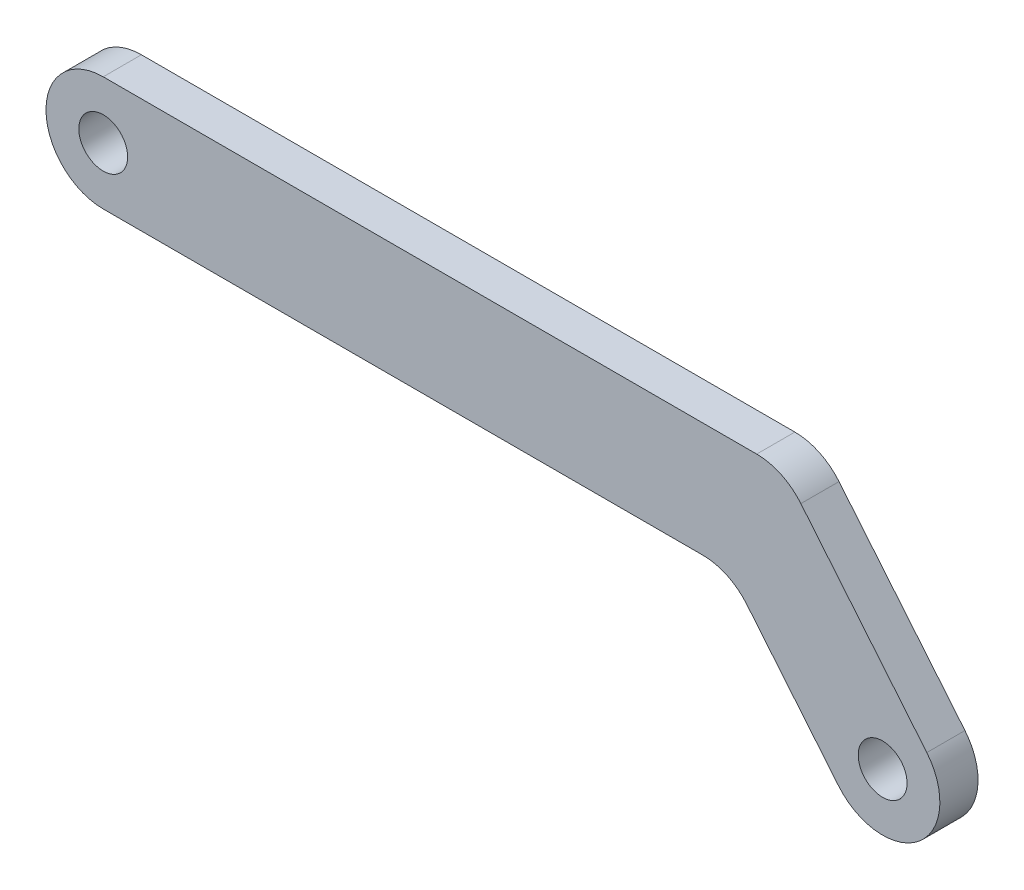
SolidWorks part; units mm, degrees
ref_plane "Front Plane" through (0, 0, 0) normal (0, 0, 1) x (1, 0, 0)
ref_plane "Top Plane" through (0, 0, 0) normal (0, 1, 0) x (1, 0, 0)
ref_plane "Right Plane" through (0, 0, 0) normal (1, 0, 0) x (0, 0, -1)
sketch "Sketch1" plane through (0, 0, 0) normal (0, 0, 1) x (1, 0, 0)
  line L0 (-64.8477, 17.4625) -> (-10.4775, 17.4625)
  line L1 (-6.8038, 15.7308) -> (3.6737, 3.0308)
  line L2 (-3.6737, -3.0308) -> (-11.2938, 6.2058)
  line L3 (-14.9675, 7.9375) -> (-64.8477, 7.9375)
  circle A0 centre (0, 0) radius 2.032
  circle A1 centre (-64.8477, 12.7) radius 2.032
  arc A2 (-64.8477, 17.4625) -> (-64.8477, 7.9375) centre (-64.8477, 12.7) ccw
  arc A3 (-3.6737, -3.0308) -> (3.6737, 3.0308) centre (0, 0) ccw
  arc A4 (-11.2938, 6.2058) -> (-14.9675, 7.9375) centre (-14.9675, 3.175) ccw
  arc A5 (-6.8038, 15.7308) -> (-10.4775, 17.4625) centre (-10.4775, 12.7) ccw
  point P5 (-29.0686, 9.7442)
  point P6 (0, 0)
  point P11 (-22.7671, 18.4534)
  point P14 (-19.5846, 19.05)
  point P19 (-12.7, 22.741)
  point P20 (-8.2271, 15.5687)
  point P21 (-9.6929, 14.4441)
  point P23 (-0.241, 0.0435)
  dimension "D1" = 66.0796
  dimension "D2" = 4.064
  dimension "D3" = 9.525
  dimension "D4" = 12.7
  dimension "D5" = 10.4775
  dimension "D6" = 12.7
extrude "Boss-Extrude1" add sketch "Sketch1" along normal blind 3.175
